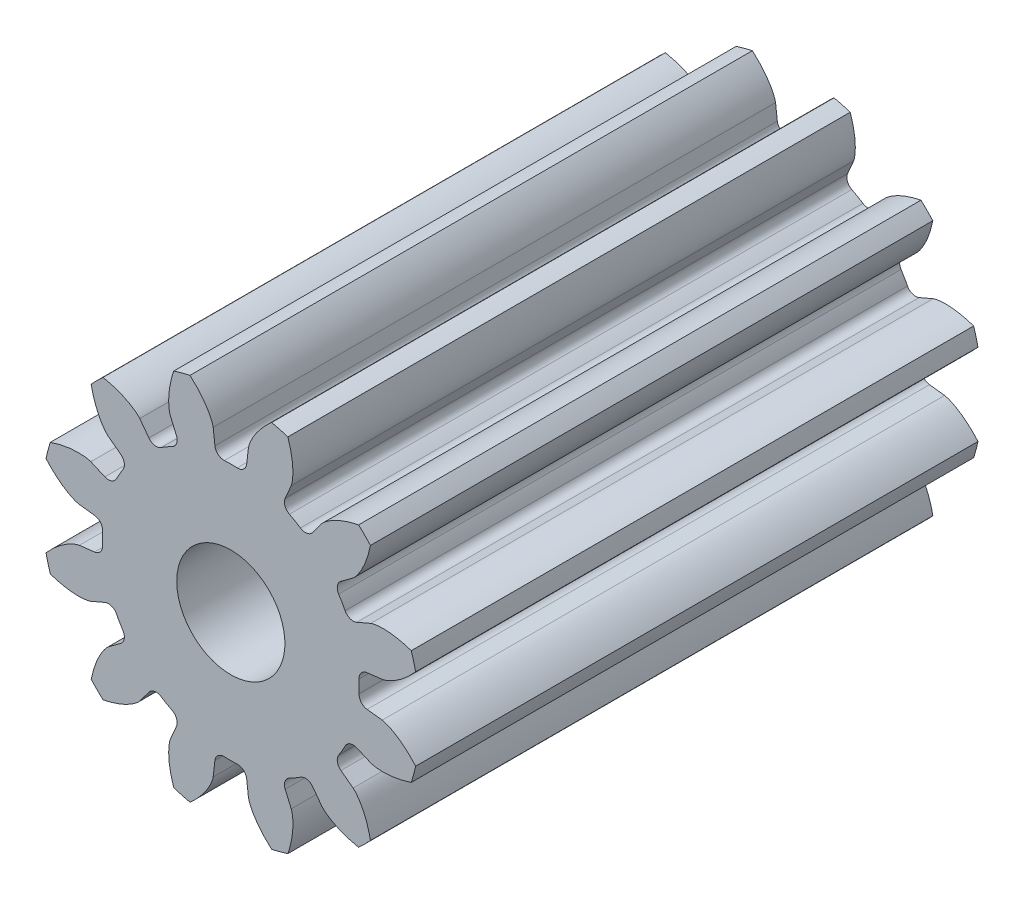
SolidWorks part; units mm, degrees
ref_plane "Front Plane" through (0, 0, 0) normal (0, 0, 1) x (1, 0, 0)
ref_plane "Top Plane" through (0, 0, 0) normal (0, 1, 0) x (1, 0, 0)
ref_plane "Right Plane" through (0, 0, 0) normal (1, 0, 0) x (0, 0, -1)
sketch "Sketch1" plane through (0, 0, 0) normal (0, 0, 1) x (1, 0, 0)
  line L0 (0, 0) -> (0, 4.7625) construction
  line L1 (-1.5306, 5.3196) -> (1.5306, 4.2054) construction
  circle A0 centre (0, 0) radius 3.7703 construction
  circle A1 centre (0, 0) radius 5.5562 construction
  circle A2 centre (0, 0) radius 4.7625 construction
  circle A3 centre (0, 0) radius 4.4753 construction
  point P8 (406.4, 0)
  point P13 (152.4, 0)
  dimension "OD | Outside Diameter" = 11.1125
  dimension "Root Diameter" = 7.5406
  dimension "Gear Pitch Diameter" = 9.525
  dimension "Base Diameter" = 8.9506
  dimension "Pressure Angle" = 20
  dimension "Number of Teeth" = 304.8
  dimension "Gear Pitch | Diametral Pitch" = 812.8
sketch "Sketch2" plane through (0, 0, 0) normal (1, 0, 0) x (0, 0, -1)
  line L0 (-152.4, 0) -> (152.4, 0) construction
  point P2 (-146.8438, 0)
  point P5 (-144.0656, 0)
  point P6 (146.8438, 0)
  dimension "Length" = 304.8
  dimension "D1" = 5.5562
  dimension "D2" = 8.3344
  dimension "D3" = 5.5562
sketch "Sketch3" plane through (0, 0, 0) normal (0, 0, 1) x (1, 0, 0)
  circle A0 centre (0, 0) radius 5.5562
  circle A1 centre (0, 0) radius 5.5562 construction
extrude "Boss-Extrude1" add sketch "Sketch3" against normal up to vertex (152.4 mm away) and the other way up to vertex (152.4 mm away) up to point (0, 0, -152.4) other way up to point (0, 0, 152.4)
sketch "Sketch4" plane through (0, 0, 0) normal (0, 0, 1) x (1, 0, 0)
  line L0 (0, 0) -> (3.745, 0.4364) construction
  line L2 (0, 0) -> (3.745, -0.4364) construction
  line L4 (3.745, 0.4364) -> (4.4452, 0.5179)
  line L5 (4.4452, -0.5179) -> (3.745, -0.4364)
  arc A0 (3.745, 0.4364) -> (3.745, -0.4364) centre (0, 0) cw
  arc A3 (5.4254, 1.1987) -> (5.4254, -1.1987) centre (0, 0) cw
  circle A4 centre (0, 0) radius 5.5562 construction
  spline S0 degree 4 poles (4.4452, 0.5179) (4.447, 0.5182) (4.452, 0.5189) (4.4613, 0.5207) (4.4765, 0.524) (4.4957, 0.5289) (4.5203, 0.5361) (4.5491, 0.5456) (4.5805, 0.5571) (4.6143, 0.5707) (4.6477, 0.5853) (4.6807, 0.6008) (4.7133, 0.6171) (4.7525, 0.6378) (4.799, 0.6639) (4.8525, 0.6964) (4.9122, 0.7355) (4.9721, 0.7778) (5.03, 0.8214) (5.0874, 0.8676) (5.1422, 0.9139) (5.1978, 0.9642) (5.2486, 1.0117) (5.304, 1.0674) (5.3484, 1.113) (5.4053, 1.1756) (5.4385, 1.2134) (5.4767, 1.2584) (5.4934, 1.2789) (5.5037, 1.2914) knots 0 0 0 0 0 0.005377 0.015084 0.028532 0.04661 0.064855 0.092111 0.119476 0.146842 0.174209 0.201575 0.228941 0.256307 0.307035 0.361767 0.4165 0.471232 0.525964 0.580697 0.635429 0.690161 0.744894 0.799626 0.854358 0.909091 0.954545 1 1 1 1 1 construction
  spline S1 degree 4 poles (4.4452, 0.5179) (4.447, 0.5182) (4.452, 0.5189) (4.4613, 0.5207) (4.4765, 0.524) (4.4957, 0.5289) (4.5203, 0.5361) (4.5491, 0.5456) (4.5805, 0.5571) (4.6143, 0.5707) (4.6477, 0.5853) (4.6807, 0.6008) (4.7133, 0.6171) (4.7525, 0.6378) (4.799, 0.6639) (4.8525, 0.6964) (4.9122, 0.7355) (4.9721, 0.7778) (5.03, 0.8214) (5.0874, 0.8676) (5.1422, 0.9139) (5.1978, 0.9642) (5.2486, 1.0117) (5.304, 1.0674) (5.3484, 1.113) (5.393, 1.1621) (5.4145, 1.1862) (5.4254, 1.1987) knots 0 0 0 0 0 0.005377 0.015084 0.028532 0.04661 0.064855 0.092111 0.119476 0.146842 0.174209 0.201575 0.228941 0.256307 0.307035 0.361767 0.4165 0.471232 0.525964 0.580697 0.635429 0.690161 0.744894 0.799626 0.854358 0.909091 0.909091 0.909091 0.909091 0.909091
  spline S2 degree 4 poles (4.4452, -0.5179) (4.447, -0.5182) (4.452, -0.5189) (4.4613, -0.5207) (4.4765, -0.524) (4.4957, -0.5289) (4.5203, -0.5361) (4.5491, -0.5456) (4.5805, -0.5571) (4.6143, -0.5707) (4.6477, -0.5853) (4.6807, -0.6008) (4.7133, -0.6171) (4.7525, -0.6378) (4.799, -0.6639) (4.8525, -0.6964) (4.9122, -0.7355) (4.9721, -0.7778) (5.03, -0.8214) (5.0874, -0.8676) (5.1422, -0.9139) (5.1978, -0.9642) (5.2486, -1.0117) (5.304, -1.0674) (5.3484, -1.113) (5.4053, -1.1756) (5.4385, -1.2134) (5.4767, -1.2584) (5.4934, -1.2789) (5.5037, -1.2914) knots 0 0 0 0 0 0.005377 0.015084 0.028532 0.04661 0.064855 0.092111 0.119476 0.146842 0.174209 0.201575 0.228941 0.256307 0.307035 0.361767 0.4165 0.471232 0.525964 0.580697 0.635429 0.690161 0.744894 0.799626 0.854358 0.909091 0.954545 1 1 1 1 1 construction
  spline S3 degree 4 poles (4.4452, -0.5179) (4.447, -0.5182) (4.452, -0.5189) (4.4613, -0.5207) (4.4765, -0.524) (4.4957, -0.5289) (4.5203, -0.5361) (4.5491, -0.5456) (4.5805, -0.5571) (4.6143, -0.5707) (4.6477, -0.5853) (4.6807, -0.6008) (4.7133, -0.6171) (4.7525, -0.6378) (4.799, -0.6639) (4.8525, -0.6964) (4.9122, -0.7355) (4.9721, -0.7778) (5.03, -0.8214) (5.0874, -0.8676) (5.1422, -0.9139) (5.1978, -0.9642) (5.2486, -1.0117) (5.304, -1.0674) (5.3484, -1.113) (5.393, -1.1621) (5.4145, -1.1862) (5.4254, -1.1987) knots 0 0 0 0 0 0.005377 0.015084 0.028532 0.04661 0.064855 0.092111 0.119476 0.146842 0.174209 0.201575 0.228941 0.256307 0.307035 0.361767 0.4165 0.471232 0.525964 0.580697 0.635429 0.690161 0.744894 0.799626 0.854358 0.909091 0.909091 0.909091 0.909091 0.909091
  dimension "D1" = 7.5406
extrude "Cut-Extrude1" cut sketch "Sketch4" against normal through all both and the other way through all
fillet "Fillet1" radius 0.2663 2 edges at (3.745, -0.4364, 0) (3.745, 0.4364, 0)
pattern_circular "CirPattern1" count 12 over 360 about axis through (0, 0, 152.4) along (0, 0, -1) of "Cut-Extrude1", "Fillet1"
sketch "Sketch6" plane through (0, 0, 152.4) normal (0, 0, 1) x (1, 0, 0)
  circle A0 centre (0, 0) radius 6.35
  dimension "D1" = 12.7
extrude "Cut-Extrude2" cut sketch "Sketch6" against normal blind 288.29
sketch "Sketch7" plane through (0, 0, -152.4) normal (0, 0, -1) x (-1, 0, 0)
  point P0 (0, 0)
hole_wizard "1/8 (0.125) Diameter Hole1" positions "Sketch7" profile "Sketch8" hole size "1/8" standard "ANSI Inch" end condition through all
sketch "Sketch8" plane through (0, 0, -152.4) normal (1, 0, 0) x (0, 1, 0)
  line L0 (0, 0) -> (0, 16.51)
  line L1 (0, 16.51) -> (1.5875, 16.51)
  line L2 (1.5875, 16.51) -> (1.5875, 0)
  line L5 (1.5875, 0) -> (0, 0)
  line L11 (0, -6.35) -> (0, 107.95) construction
  dimension "Thru Hole Dia." = 3.175
  dimension "Thru Hole Depth" = 16.51
equation "\"Root Diameter@Sketch1\"=\"Root Diameter\""
equation "\"OD | Outside Diameter@Sketch1\"=\"Outside Diameter\""
equation "\"D1@CirPattern1\"=\"Number of Teeth\""
equation "\"Diametral Pitch\"=32"
equation "\"Number of Teeth\"=12"
equation "\"Pressure Angle\"=20"
equation "\"Pitch Diameter\"= \"Number of Teeth\" / \"Diametral Pitch\""
equation "\"Base Diameter\"= \"Pitch Diameter\" * cos ( \"Pressure Angle\" )"
equation "\"Outside Diameter\"= ( \"Number of Teeth\" + 2 ) / \"Diametral Pitch\""
equation "\"Dedendum\"= 1.25 / \"Diametral Pitch\""
equation "\"Root Diameter\"= \"Pitch Diameter\" - ( 2 * \"Dedendum\" )"
equation "\"Pitch Angle\"= 360deg / \"Number of Teeth\""
equation "\"Alpha\"= sqr ( \"Pitch Diameter\" ^ 2 - \"Base Diameter\" ^ 2 ) / \"Base Diameter\" * 180 / PI - \"Pressure Angle\""
equation "\"Beta\"= ( \"Pitch Angle\" / 4 - \"Alpha\" )"
equation "\"Phi\"= sqr ( ( \"Outside Diameter\" / 2 ) ^ 2 - ( \"Base Diameter\" / 2 ) ^ 2 ) / ( \"Base Diameter\" / 2 )"
equation "\"Addendum\"= 1 / \"Diametral Pitch\""
equation "\"WorkingDepth\"= 2 / \"Diametral Pitch\""
equation "\"WholeDepth\"= 2.25 / \"Diametral Pitch\""
equation "\"Clearance\"= 0.25 / \"Diametral Pitch\""
equation "\"ToothThickness\"= ( pi * 2 ) / \"Diametral Pitch\""
equation "\"CircularPitch\"= pi / \"Diametral Pitch\""
equation "\"Number of Teeth@Sketch1\"=\"Number of Teeth\""
equation "\"Gear Pitch | Diametral Pitch@Sketch1\"=\"Diametral Pitch\""
equation "\"Pressure Angle@Sketch1\"=\"Pressure Angle\""
equation "\"Gear Pitch Diameter@Sketch1\"=\"Pitch Diameter\""
equation "\"Base Diameter@Sketch1\"=\"Base Diameter\""
equation "\"Fillet\"= \"Clearance\" * cos ( \"Pressure Angle\" ) * tan ( ( 90 + \"Pressure Angle\" ) / 2 )"
equation "\"D1@Fillet1\"=\"Fillet\""
equation "\"D1@Sketch4\"=if( \"Base Diameter\">\"Root Diameter\",\"Root Diameter\",\"Base Diameter\"-.00001)"
equation "\"D1@Sketch2\"=\"OD | Outside Diameter@Sketch1\"*2*0.5*0.5"
equation "\"D2@Sketch2\"=\"D1@Sketch2\"*1.5"
equation "\"D3@Sketch2\"=\"D1@Sketch2\""
